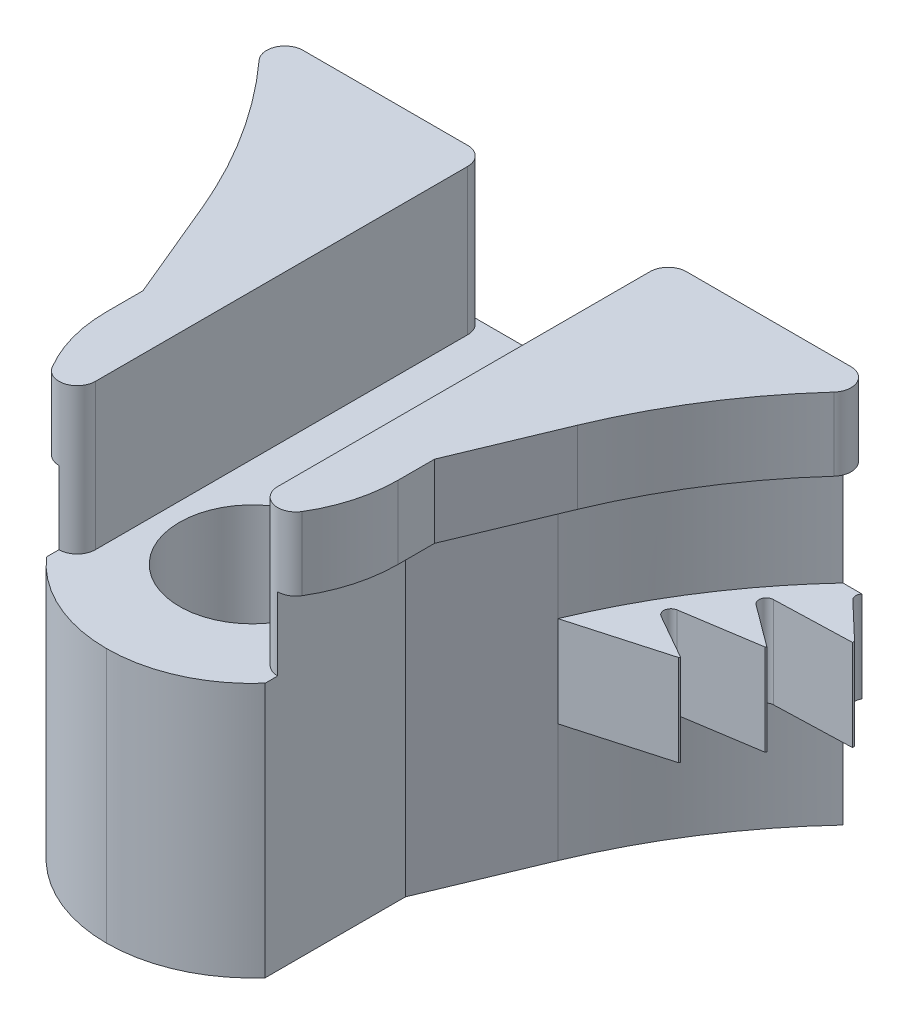
SolidWorks part; units mm, degrees
ref_plane "Front Plane" through (0, 0, 0) normal (0, 0, 1) x (1, 0, 0)
ref_plane "Top Plane" through (0, 0, 0) normal (0, 1, 0) x (1, 0, 0)
ref_plane "Right Plane" through (0, 0, 0) normal (1, 0, 0) x (0, 0, -1)
sketch "Sketch1" plane through (0, 0, 0) normal (0, 1, 0) x (1, 0, 0)
  line L0 (0, 0) -> (0, 25.4) construction
  line L1 (-22.86, 25.4) -> (22.86, 25.4)
  line L2 (22.86, 25.4) -> (22.86, 21.5476)
  line L3 (-5.08, 0) -> (5.08, 0)
  line L4 (5.08, 0) -> (5.08, 6.35)
  line L5 (5.08, 6.35) -> (6.5454, 9.8669)
  line L6 (-22.86, 25.4) -> (-22.86, 21.5476)
  line L7 (-5.08, 6.35) -> (-6.5454, 9.8669)
  line L8 (-5.08, 0) -> (-5.08, 6.35)
  arc A0 (22.86, 21.5476) -> (6.5454, 9.8669) centre (24.13, 2.54) ccw
  arc A2 (-22.86, 21.5476) -> (-6.5454, 9.8669) centre (-24.13, 2.54) cw
  dimension "D1" = 38.1
  dimension "D2" = 5.08
  dimension "D3" = 22.86
  dimension "D4" = 6.35
  dimension "0.9" = 24.13
  dimension "D6" = 2.54
  dimension "D7" = 25.4
extrude "Boss-Extrude1" add sketch "Sketch1" along normal blind 2.54
sketch "Sketch3" plane through (0, 0, 0) normal (0, -1, 0) x (1, 0, 0)
  line L8 (-3.81, 0) -> (0, 0)
  line L9 (-5.08, 0) -> (5.08, 0) construction
  line L10 (0, 0) -> (0, -25.4)
  line L11 (-21.59, -25.4) -> (-21.59, -22.7006)
  line L12 (-5.3731, -10.3554) -> (-3.81, -6.604)
  line L13 (-3.81, -6.604) -> (-3.81, 0)
  line L15 (-5.3731, -10.3554) -> (-3.81, -6.604)
  line L16 (-3.81, -6.604) -> (-3.81, 0)
  line L17 (22.86, -25.4) -> (-22.86, -25.4) construction
  line L18 (0, -25.4) -> (-21.59, -25.4)
  line L19 (-21.59, -22.7006) -> (-22.86, -22.7006)
  line L20 (-22.86, -25.4) -> (-22.86, -21.5476) construction
  line L21 (-22.86, -22.7006) -> (-22.86, -25.4)
  line L22 (-22.86, -25.4) -> (-21.59, -25.4)
  arc A3 (-21.59, -22.7006) -> (-5.3731, -10.3554) centre (-24.13, -2.54) ccw
  arc A4 (-21.59, -22.7006) -> (-5.3731, -10.3554) centre (-24.13, -2.54) ccw
  dimension "D1" = 1.27
extrude "Boss-Extrude2" add sketch "Sketch3" along normal blind 11.43
ref_plane "Plane1" through (0, -5.715, 0) normal (0, -1, 0) x (-1, 0, 0)
sketch "Sketch4" plane through (0, -5.715, 0) normal (0, -1, 0) x (-1, 0, 0)
  line L5 (22.9447, 20.2804) -> (22.9447, 25.4)
  line L6 (22.9447, 25.4) -> (0, 25.4)
  line L7 (7.7177, 9.3785) -> (6.35, 6.096)
  line L8 (6.35, 6.096) -> (6.35, 0)
  line L11 (0, 25.4) -> (0, 0) construction
  line L12 (22.86, 25.4) -> (0, 25.4) construction
  line L13 (0, 25.4) -> (0, 0)
  line L14 (0, 0) -> (3.81, 0)
  line L15 (7.7177, 9.3785) -> (4.966, 9.3785)
  line L16 (4.966, 9.3785) -> (3.81, 6.604)
  line L17 (3.81, 6.604) -> (3.81, 0)
  line L18 (3.81, 0) -> (3.81, 6.604) construction
  line L19 (3.81, 6.604) -> (5.3731, 10.3554) construction
  arc A2 (22.9447, 20.2804) -> (7.7177, 9.3785) centre (24.13, 2.54) ccw
  arc A3 (22.9447, 20.2804) -> (7.7177, 9.3785) centre (24.13, 2.54) ccw
  point P14 (6.236, 9.3785)
  dimension "D1" = 1.27
extrude "Boss-Extrude3" add sketch "Sketch4" along normal mid plane 3.175
sketch "Sketch6" plane through (0, -7.3025, 0) normal (0, -1, 0) x (1, 0, 0)
  line L0 (-7.7177, -9.3785) -> (-5.3731, -10.3554)
  line L1 (-5.3731, -10.3554) -> (-8.6484, -11.2835)
  line L2 (-8.6484, -11.2835) -> (-7.7177, -9.3785)
  line L3 (-3.81, -6.604) -> (-5.3731, -10.3554) construction
  arc A0 (-21.59, -22.7006) -> (-5.3731, -10.3554) centre (-24.13, -2.54) ccw construction
  arc A1 (-22.9447, -20.2804) -> (-7.7177, -9.3785) centre (-24.13, -2.54) ccw construction
  point P6 (-6.236, -9.3785)
  dimension "D1" = 1.905
extrude "Cut-Extrude1" cut sketch "Sketch6" against normal blind 5.08
sketch "Sketch7" plane through (0, -7.3025, 0) normal (0, -1, 0) x (1, 0, 0)
  line L6 (-7.7177, -9.3785) -> (-5.3731, -10.3554)
  line L7 (-5.3731, -10.3554) -> (-4.966, -9.3785)
  line L8 (-4.966, -9.3785) -> (-7.7177, -9.3785)
  line L9 (-7.7177, -9.3785) -> (-5.3731, -10.3554)
  line L10 (-5.3731, -10.3554) -> (-4.966, -9.3785)
  line L11 (-4.966, -9.3785) -> (-7.7177, -9.3785)
  dimension "D1" = 0
extrude "Cut-Extrude2" cut sketch "Sketch7" against normal blind 5.08
pattern_circular "CirPattern1" count 10 over 63 about axis through (-24.13, 0, -2.54) along (0, 1, 0) of "Cut-Extrude1"
fillet "Fillet1" radius 0.254 9 edges at (-22.5781, -4.7625, -22.8007) (-20.1205, -5.715, -22.4605) (-17.7227, -5.715, -21.8234) (-15.4204, -5.715, -20.8988) (-13.2479, -5.715, -19.7005) (-11.2377, -5.715, -18.2464) (-9.4197, -5.715, -16.5582) (-7.821, -5.715, -14.6609) (-6.4653, -5.715, -12.583)
mirror "Mirror1" about plane through (0, -11.43, 0) normal (-1, 0, 0) of "Fillet1", "CirPattern1", "Cut-Extrude2", "Cut-Extrude1", "Boss-Extrude2", "Boss-Extrude3"
fillet "Fillet3" radius 5.08 2 edges at (5.08, 1.27, 0) (-5.08, 1.27, 0)
sketch "Sketch8" plane through (0, -11.43, 0) normal (0, -1, 0) x (1, 0, 0)
  circle A0 centre (0, -5.08) radius 2.54
  point P3 (0, -5.08)
  dimension "D1" = 5.08
extrude "Cut-Extrude3" cut sketch "Sketch8" against normal through all
sketch "Sketch9" plane through (0, 0, -25.4) normal (0, 0, 1) x (1, 0, 0)
  line L1 (3.175, -2.54) -> (-3.175, -2.54)
  line L2 (3.175, -2.54) -> (3.175, 2.54)
  line L3 (3.175, 2.54) -> (-3.175, 2.54)
  line L4 (-3.175, -2.54) -> (-3.175, 2.54)
  line L5 (3.175, -2.54) -> (-3.175, 2.54) construction
  line L6 (3.175, 2.54) -> (-3.175, -2.54) construction
  point P0 (0, 0)
  dimension "D1" = 6.35
  dimension "D2" = 5.08
extrude "Cut-Extrude4" cut sketch "Sketch9" along normal through all
fillet "Fillet4" [suppressed] radius 1.27
fillet "Fillet5" radius 1.27 8 edges at (-22.86, 1.27, -21.5476) (-22.86, -9.3662, -22.7006) (-22.86, -2.0637, -22.7006) (22.86, 1.27, -21.5476) (22.86, -2.0637, -22.7006) (22.86, -9.3662, -22.7006) (22.86, -0.7937, -25.4) (-22.86, -0.7937, -25.4)
fillet "Fillet6" radius 0.635 2 edges at (3.175, 0, -1.1144) (-3.175, 0, -1.1144)
sketch "Sketch10" plane through (0, 2.54, 0) normal (0, 1, 0) x (1, 0, 0)
  line L0 (-3.175, 25.4) -> (-21.59, 25.4) construction
  line L1 (-11.2235, 25.4) -> (-23.5117, 25.4)
  line L2 (-11.2235, 25.4) -> (-11.2235, 2.6061)
  line L3 (-11.2235, 2.6061) -> (-23.5117, 2.6061)
  line L4 (-23.5117, 25.4) -> (-23.5117, 2.6061)
  line L5 (0, 0) -> (0, 25.4) construction
  line L6 (-3.175, 25.4) -> (3.175, 25.4) construction
  line L7 (23.5117, 25.4) -> (23.5117, 2.6061)
  line L8 (11.2235, 2.6061) -> (23.5117, 2.6061)
  line L9 (11.2235, 25.4) -> (11.2235, 2.6061)
  line L10 (11.2235, 25.4) -> (23.5117, 25.4)
extrude "Cut-Extrude5" cut sketch "Sketch10" against normal through all
sketch "Sketch11" plane through (0, 2.54, 0) normal (0, 1, 0) x (1, 0, 0)
  line L1 (-11.2235, 25.4) -> (11.2235, 25.4)
  line L2 (-11.2235, 25.4) -> (-11.2235, 16.3947)
  line L3 (-11.2235, 16.3947) -> (11.2235, 16.3947)
  line L4 (11.2235, 25.4) -> (11.2235, 16.3947)
extrude "Cut-Extrude6" cut sketch "Sketch11" against normal through all
fillet "Fillet7" radius 0.635 4 edges at (-3.175, 0, -16.3947) (3.175, 0, -16.3947) (11.0552, 1.27, -16.3947) (-11.0552, 1.27, -16.3947)
